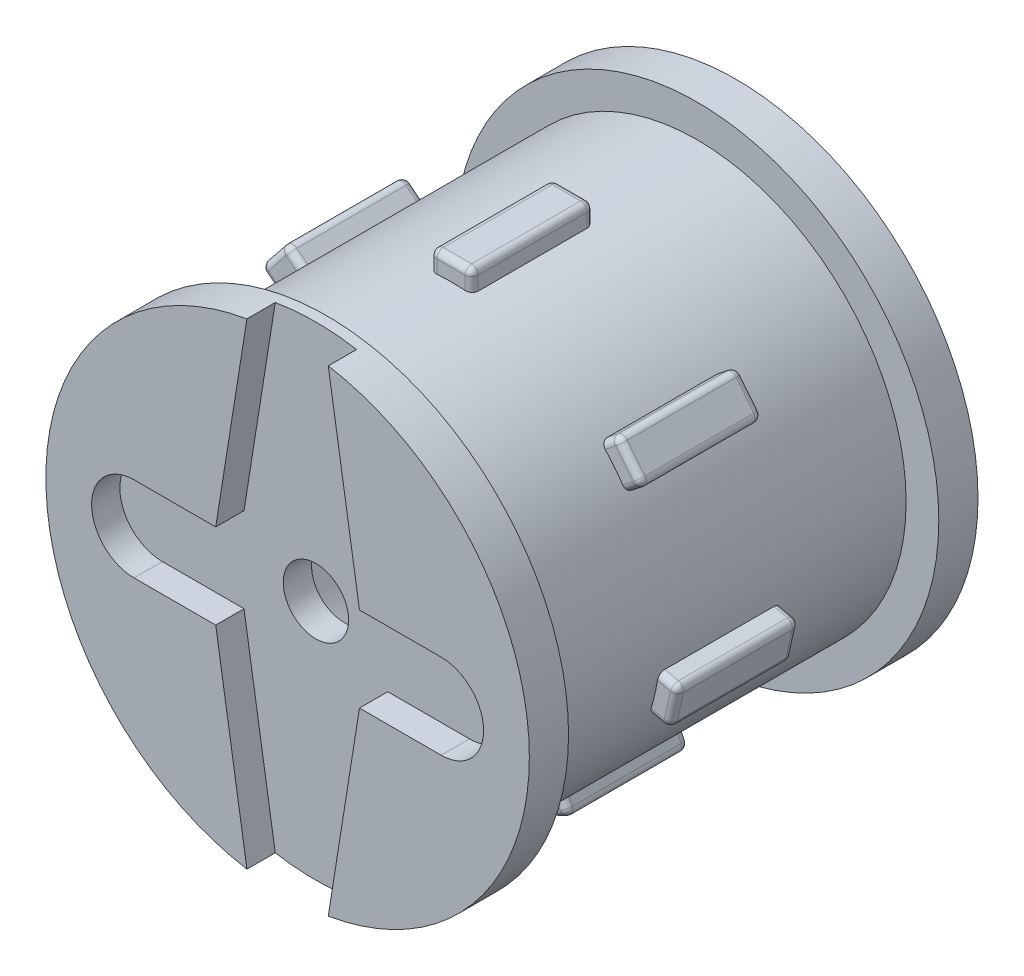
SolidWorks part; units mm, degrees
ref_plane "Ebene vorne" through (0, 0, 0) normal (0, 0, 1) x (1, 0, 0)
ref_plane "Ebene oben" through (0, 0, 0) normal (0, 1, 0) x (1, 0, 0)
ref_plane "Ebene rechts" through (0, 0, 0) normal (1, 0, 0) x (0, 0, -1)
sketch "Skizze1" plane through (0, 0, 0) normal (0, 0, 1) x (1, 0, 0)
  circle A0 centre (0, 0) radius 9.6
  dimension "D1" = 19.2
extrude "Aufsatz-Linear austragen1" add sketch "Skizze1" along normal blind 10.3 and the other way blind 10.3
ref_axis "Rotationsachse" through (0, 0, -10.3) along (0, 0, 1)
sketch "Skizze2" plane through (0, 0, 10.3) normal (0, 0, 1) x (1, 0, 0)
  circle A0 centre (0, 0) radius 11.1
  dimension "D1" = 22.2
extrude "Aufsatz-Linear austragen2" add sketch "Skizze2" against normal blind 1.8
sketch "Skizze3" plane through (0, 0, -10.3) normal (0, 0, -1) x (-1, 0, 0)
  circle A0 centre (0, 0) radius 11.1
  dimension "D1" = 22.2
extrude "Aufsatz-Linear austragen3" add sketch "Skizze3" against normal blind 1.8
sketch "Skizze12" plane through (0, 0, 10.3) normal (0, 0, 1) x (1, 0, 0)
  line L0 (3.3, -1.95) -> (0.95, -16.7)
  line L1 (-3.05, 1.95) -> (3.05, 1.95)
  line L2 (-3.05, 1.95) -> (-3.05, -1.95)
  line L3 (-3.05, -1.95) -> (3.05, -1.95)
  line L4 (3.05, 1.95) -> (3.05, -1.95)
  line L5 (-3.05, 1.95) -> (3.05, -1.95) construction
  line L6 (-3.05, -1.95) -> (3.05, 1.95) construction
  line L7 (3.05, 1.95) -> (7.05, 1.95)
  line L8 (3.05, 1.95) -> (3.05, -1.95)
  line L9 (3.05, -1.95) -> (7.05, -1.95)
  line L10 (7.05, 1.95) -> (7.05, -1.95)
  line L11 (-3.05, -1.95) -> (-3.3, -1.95)
  line L12 (-3.3, -1.95) -> (-0.95, -16.7)
  circle A0 centre (7.05, 0) radius 1.95
  circle A1 centre (0, -16.7) radius 0.95
  point P0 (0, 0)
  point P12 (0, -1.95)
  circle M11 centre (0, 0) radius 11.1
  dimension "D5" = 1.9
  dimension "D1" = 6.1
  dimension "D2" = 3.9
  dimension "D3" = 4
  dimension "D4" = 14.75
  dimension "D6" = 3.05
  dimension "D7" = 3.3
  dimension "D8" = 3.3
extrude "Schnitt-Linear austragen1" cut sketch "Skizze12" against normal blind 1.3 contours A1 | A1 L0 L12 M11 | L11 L12 L0 L9 L3 M11 | L4 L1 L2 L3 | A0 L7 L4 L9 | L10 A0 | L10 A0 region at (0, -6.0723, 10.3) region at (4.3226, 0, 10.3) region at (0, -13.3026, 10.3) region at (0, 0, 10.3) region at (6.2224, 0, 10.3) region at (7.8776, 0, 10.3) region at (0, -16.7, 10.3)
sketch "Skizze8" plane through (0, 0, 0) normal (1, 0, 0) x (0, 0, -1)
  line L0 (10.3, 0) -> (10.3, 8)
  line L1 (10.3, -11.1) -> (10.3, 11.1) construction
  line L2 (10.3, 8) -> (8.5, 8)
  line L3 (8.5, 11.1) -> (8.5, -11.1) construction
  line L4 (8.5, 8) -> (-7.7, 3.5)
  line L6 (-7.7, 3.5) -> (-7.7, 0)
  line L7 (-7.7, 0) -> (10.3, 0)
  dimension "D1" = 8
  dimension "D2" = 3.5
  dimension "D3" = 18
revolve "Schnitt-Rotation1" cut sketch "Skizze8" angle 360 about axis through (0, 0, -10.3) along (0, 0, 1)
ref_plane "Schnittebene_Zaehne" through (0, 0, 0) normal (0, 0, -1) x (-1, 0, 0)
sketch "Skizze11" plane through (0, 0, 0) normal (0, 0, -1) x (-1, 0, 0)
  line L0 (0, 0) -> (0, 12.664) construction
  line L6 (-0.95, 8.71) -> (0.95, 8.71)
  line L7 (-0.95, 8.71) -> (-0.95, 10.49)
  line L8 (-0.95, 10.49) -> (0.95, 10.49)
  line L9 (0.95, 8.71) -> (0.95, 10.49)
  line L10 (-0.95, 8.71) -> (0.95, 10.49) construction
  line L11 (-0.95, 10.49) -> (0.95, 8.71) construction
  circle A1 centre (0, 0) radius 9.6 construction
  point P3 (0, 9.6)
  dimension "D1" = 0.89
  dimension "D2" = 1.9
extrude "Aufsatz-Linear austragen4" add sketch "Skizze11" along normal blind 2.8 and the other way blind 2.8
pattern_circular "Kreismuster2" count 7 over 360 about axis through (0, 0, -10.3) along (0, 0, 1) of "Aufsatz-Linear austragen4"
fillet "Verrundung1" radius 0.3 56 edges at (8.2014, 6.5404, 2.8) (7.6091, 7.2831, 0) (8.2014, 6.5404, -2.8) (8.7937, 5.7977, 0) (-8.4274, 5.5055, 2.8) (-7.2428, 6.991, 2.8) (-7.2428, 6.991, -2.8) (-8.4274, 5.5055, -2.8) (-9.5588, -3.1562, -2.8) (-9.9816, -1.3038, -2.8) (-9.5588, -3.1562, 2.8) (-9.9816, -1.3038, 2.8) (-5.2041, -8.6168, -2.8) (-3.4922, -9.4412, -2.8) (-3.4922, -9.4412, 2.8) (-5.2041, -8.6168, 2.8) (5.2041, -8.6168, 2.8) (3.4922, -9.4412, 2.8) (3.4922, -9.4412, -2.8) (5.2041, -8.6168, -2.8) (9.5588, -3.1562, 2.8) (9.5588, -3.1562, -2.8) (9.9816, -1.3038, 2.8) (9.9816, -1.3038, -2.8) (8.4274, 5.5055, 2.8) (8.4274, 5.5055, -2.8) (7.2428, 6.991, -2.8) (7.2428, 6.991, 2.8) (0.95, 10.0214, 2.8) (0.95, 10.0214, -2.8) (-0.95, 10.0214, -2.8) (-0.95, 10.0214, 2.8) (10.4384, -1.4081, 0) (10.227, -2.3342, 2.8) (10.227, -2.3342, -2.8) (10.0156, -3.2604, 0) (4.5514, -9.4512, 2.8) (4.5514, -9.4512, -2.8) (5.4074, -9.039, 0) (3.6955, -9.8634, 0) (-4.5514, -9.4512, 2.8) (-4.5514, -9.4512, -2.8) (-5.4074, -9.039, 0) (-3.6955, -9.8634, 0) (-10.227, -2.3342, 2.8) (-10.227, -2.3342, -2.8) (-10.0156, -3.2604, 0) (-10.4384, -1.4081, 0) (-8.2014, 6.5404, -2.8) (-8.2014, 6.5404, 2.8) (-8.7937, 5.7977, 0) (-7.6091, 7.2831, 0) (0, 10.49, -2.8) (0, 10.49, 2.8) (0.95, 10.49, 0) (-0.95, 10.49, 0)
pattern_circular "Kreismuster3" count 2 over 360 about axis through (0, 0, -10.3) along (0, 0, 1) of "Schnitt-Linear austragen1"
sketch "Skizze14" plane through (0, 0, 10.3) normal (0, 0, 1) x (1, 0, 0)
  circle A0 centre (0, 0) radius 1.5
  dimension "D1" = 3
extrude "Schnitt-Linear austragen2" cut sketch "Skizze14" against normal up to surface (2.6 mm away) up to face at (-3.5, 0, 7.7)
